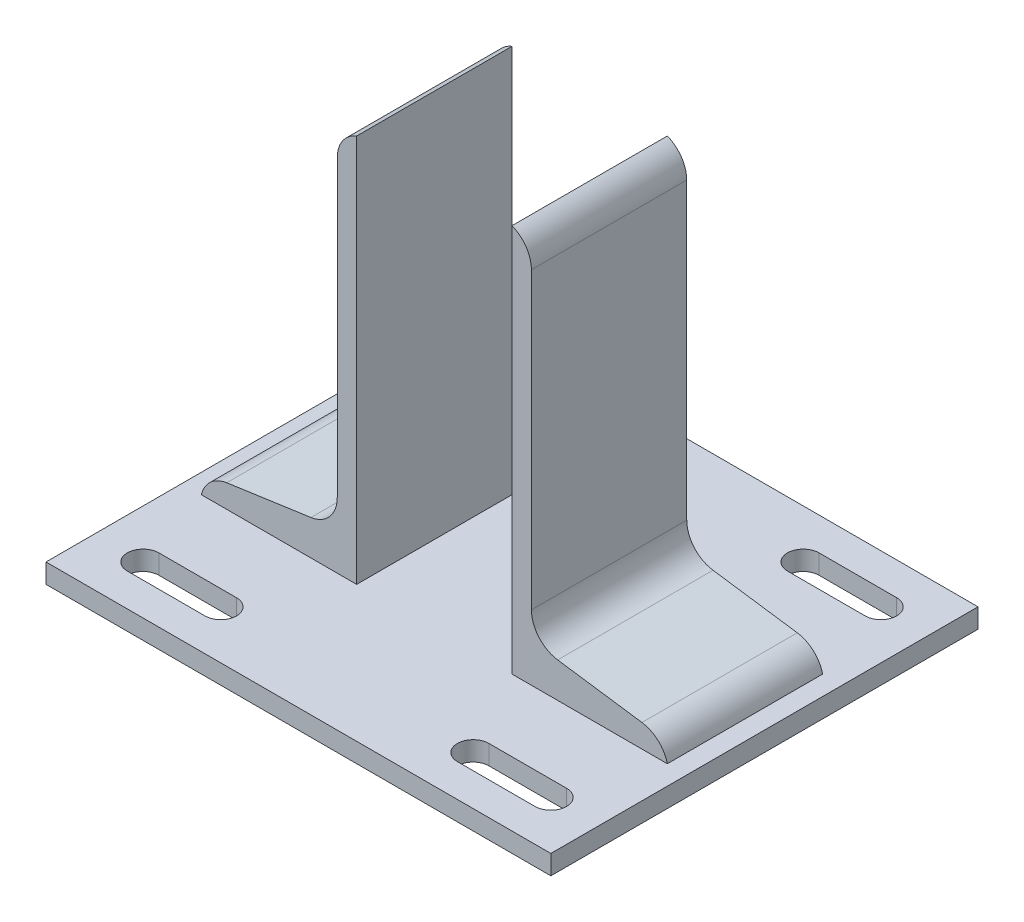
SolidWorks part; units mm, degrees
ref_plane "Front Plane" through (0, 0, 0) normal (0, 0, 1) x (1, 0, 0)
ref_plane "Top Plane" through (0, 0, 0) normal (0, 1, 0) x (1, 0, 0)
ref_plane "Right Plane" through (0, 0, 0) normal (1, 0, 0) x (0, 0, -1)
sketch "Sketch1" plane through (0, 0, 0) normal (0, 1, 0) x (1, 0, 0)
  line L0 (0, 0) -> (0, 60.0324) construction
  line L1 (0, 0) -> (-72.2441, 0) construction
  line L2 (-82.55, -69.85) -> (-82.55, 69.85)
  line L3 (-82.55, 69.85) -> (82.55, 69.85)
  line L4 (82.55, -69.85) -> (82.55, 69.85)
  line L5 (-82.55, -69.85) -> (82.55, -69.85)
  point P8 (0, 69.85)
  point P10 (82.55, 0)
  point P11 (-82.55, 0)
  dimension "D1" = 165.1
  dimension "D2" = 139.7
extrude "Boss-Extrude1" add sketch "Sketch1" along normal blind 6.35
sketch "Sketch2" plane through (0, 6.35, 0) normal (0, 1, 0) x (1, 0, 0)
  line L0 (0, 0) -> (82.55, 0) construction
  line L1 (82.55, -69.85) -> (82.55, 69.85) construction
  line L2 (25.4, -25.4) -> (25.4, 25.4)
  line L3 (25.4, 25.4) -> (76.2, 25.4)
  line L4 (76.2, 25.4) -> (76.2, -25.4)
  line L5 (25.4, -25.4) -> (76.2, -25.4)
  point P10 (76.2, 0)
  point P11 (25.4, 0)
  dimension "D1" = 50.8
  dimension "D2" = 50.8
  dimension "D3" = 6.35
extrude "Boss-Extrude2" add sketch "Sketch2" along normal blind 127
sketch "Sketch4" plane through (0, 0, 25.4) normal (0, 0, 1) x (1, 0, 0)
  line L0 (31.75, 133.35) -> (31.75, 19.05)
  line L1 (25.4, 133.35) -> (76.2, 133.35) construction
  line L2 (31.75, 19.05) -> (76.2, 12.7)
  line L3 (76.2, 133.35) -> (76.2, 6.35) construction
  line L4 (76.2, 12.7) -> (95.9547, 12.7)
  line L5 (95.9547, 12.7) -> (95.9547, 161.1387)
  line L6 (95.9547, 161.1387) -> (31.75, 161.1387)
  line L7 (31.75, 161.1387) -> (31.75, 133.35)
  line L8 (25.4, 133.35) -> (25.4, 6.35) construction
  line L9 (-82.55, 6.35) -> (82.55, 6.35) construction
  line L10 (25.4, 6.35) -> (76.2, 6.35) construction
  dimension "D1" = 6.35
  dimension "D2" = 6.35
  dimension "D3" = 12.7
extrude "Cut-Extrude1" cut sketch "Sketch4" against normal through all
fillet "Fillet1" radius 10 3 edges at (76.2, 12.7, 0) (31.75, 19.05, 0) (31.75, 133.35, 0)
mirror "Mirror6" about plane through (0, 0, 0) normal (1, 0, 0) of "Fillet1", "Cut-Extrude1", "Boss-Extrude2"
sketch "Sketch6" plane through (0, 6.35, 0) normal (0, 1, 0) x (-1, 0, 0)
  line L0 (82.55, 0) -> (-82.55, 0) construction
  line L1 (82.55, -69.85) -> (82.55, 69.85) construction
  line L2 (-82.55, 69.85) -> (-82.55, -69.85) construction
  line L3 (0, -69.85) -> (0, 69.85) construction
  line L4 (-82.55, -69.85) -> (82.55, -69.85) construction
  line L5 (82.55, 69.85) -> (-82.55, 69.85) construction
  line L6 (-41.275, 48.8188) -> (-66.675, 48.8188)
  line L7 (-41.275, 59.1312) -> (-66.675, 59.1312)
  line L8 (-41.275, -59.1312) -> (-66.675, -59.1312)
  line L9 (-41.275, -48.8188) -> (-66.675, -48.8188)
  line L10 (41.275, 59.1312) -> (66.675, 59.1312)
  line L11 (41.275, 48.8188) -> (66.675, 48.8188)
  line L12 (41.275, -48.8188) -> (66.675, -48.8188)
  line L13 (41.275, -59.1312) -> (66.675, -59.1312)
  arc A0 (-41.275, 48.8188) -> (-41.275, 59.1312) centre (-41.275, 53.975) ccw
  arc A1 (-66.675, 48.8188) -> (-66.675, 59.1312) centre (-66.675, 53.975) cw
  arc A2 (-66.675, -48.8188) -> (-66.675, -59.1312) centre (-66.675, -53.975) ccw
  arc A3 (-41.275, -48.8188) -> (-41.275, -59.1312) centre (-41.275, -53.975) cw
  arc A4 (66.675, 48.8188) -> (66.675, 59.1312) centre (66.675, 53.975) ccw
  arc A5 (41.275, 48.8188) -> (41.275, 59.1312) centre (41.275, 53.975) cw
  arc A6 (41.275, -48.8188) -> (41.275, -59.1312) centre (41.275, -53.975) ccw
  arc A7 (66.675, -48.8188) -> (66.675, -59.1312) centre (66.675, -53.975) cw
  dimension "D1" = 10.3124
  dimension "D2" = 107.95
  dimension "D3" = 25.4
  dimension "D4" = 82.55
extrude "Cut-Extrude2" cut sketch "Sketch6" against normal blind 127
